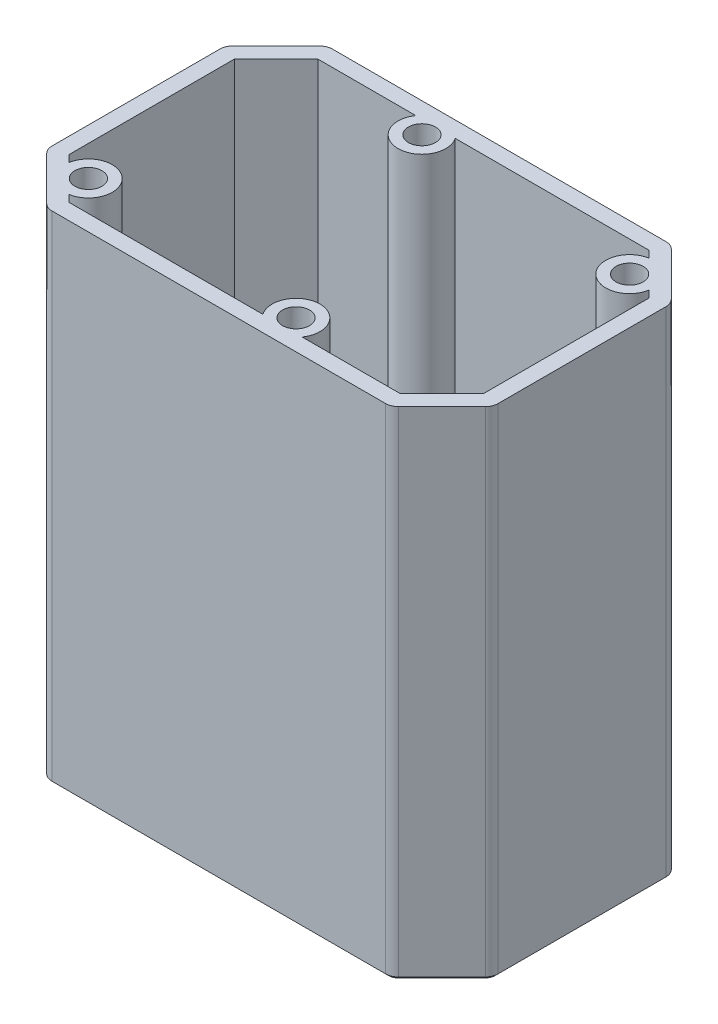
SolidWorks part; units mm, degrees
ref_plane "Front Plane" through (0, 0, 0) normal (0, 0, 1) x (1, 0, 0)
ref_plane "Top Plane" through (0, 0, 0) normal (0, 1, 0) x (1, 0, 0)
ref_plane "Right Plane" through (0, 0, 0) normal (1, 0, 0) x (0, 0, -1)
sketch "Sketch1" plane through (0, 0, 0) normal (0, 1, 0) x (1, 0, 0)
  line L0 (26.1716, 22) -> (-26.1716, 22)
  line L1 (-27.5858, 21.4142) -> (-34.4142, 14.5858)
  line L2 (-35, 13.1716) -> (-35, -13.1716)
  line L3 (-34.4142, -14.5858) -> (-27.5858, -21.4142)
  line L4 (-26.1716, -22) -> (26.1716, -22)
  line L5 (27.5858, -21.4142) -> (34.4142, -14.5858)
  line L6 (35, -13.1716) -> (35, 13.1716)
  line L7 (34.4142, 14.5858) -> (27.5858, 21.4142)
  line L8 (0, 22) -> (0, -22) construction
  line L9 (-32.5, 12.9645) -> (-32.5, -12.9645)
  line L10 (35, 0) -> (-35, 0) construction
  line L11 (-32.5, -12.9645) -> (-25.9645, -19.5)
  line L12 (-25.9645, -19.5) -> (25.9645, -19.5)
  line L13 (25.9645, -19.5) -> (32.5, -12.9645)
  line L14 (32.5, -12.9645) -> (32.5, 12.9645)
  line L15 (32.5, 12.9645) -> (25.9645, 19.5)
  line L16 (25.9645, 19.5) -> (-25.9645, 19.5)
  line L17 (-25.9645, 19.5) -> (-32.5, 12.9645)
  line L18 (-31, -18) -> (-29.2322, -16.2322) construction
  line L19 (31, 18) -> (29.2322, 16.2322) construction
  circle A3 centre (7.5, -17.375) radius 2.125
  circle A4 centre (27.7296, 14.7296) radius 2.125
  circle A5 centre (-7.5, 17.375) radius 2.125
  circle A6 centre (-27.7296, -14.7296) radius 2.125
  arc A9 (-26.1716, 22) -> (-27.5858, 21.4142) centre (-26.1716, 20) ccw
  arc A10 (-34.4142, 14.5858) -> (-35, 13.1716) centre (-33, 13.1716) ccw
  arc A11 (-35, -13.1716) -> (-34.4142, -14.5858) centre (-33, -13.1716) ccw
  arc A12 (-27.5858, -21.4142) -> (-26.1716, -22) centre (-26.1716, -20) ccw
  arc A13 (26.1716, -22) -> (27.5858, -21.4142) centre (26.1716, -20) ccw
  arc A14 (34.4142, -14.5858) -> (35, -13.1716) centre (33, -13.1716) ccw
  arc A15 (35, 13.1716) -> (34.4142, 14.5858) centre (33, 13.1716) ccw
  arc A16 (27.5858, 21.4142) -> (26.1716, 22) centre (26.1716, 20) ccw
  arc A21 (-32.5, -12.9645) -> (-32.5, -12.9645) centre (-32.5, -12.9645) ccw
  arc A22 (-25.9645, -19.5) -> (-25.9645, -19.5) centre (-25.9645, -19.5) ccw
  arc A23 (25.9645, -19.5) -> (25.9645, -19.5) centre (25.9645, -19.5) ccw
  arc A24 (32.5, -12.9645) -> (32.5, -12.9645) centre (32.5, -12.9645) ccw
  arc A25 (32.5, 12.9645) -> (32.5, 12.9645) centre (32.5, 12.9645) ccw
  arc A26 (25.9645, 19.5) -> (25.9645, 19.5) centre (25.9645, 19.5) ccw
  arc A27 (-25.9645, 19.5) -> (-25.9645, 19.5) centre (-25.9645, 19.5) ccw
  arc A28 (-32.5, 12.9645) -> (-32.5, 12.9645) centre (-32.5, 12.9645) ccw
  circle A29 centre (-7.5, 17.375) radius 3.75
  circle A30 centre (7.5, -17.375) radius 3.75
  circle A31 centre (27.7296, 14.7296) radius 3.75
  circle A32 centre (-27.7296, -14.7296) radius 3.75
  dimension "D2" = 7.5
  dimension "D4" = 4.25
  dimension "D1" = 44
  dimension "D5" = 70
  dimension "D6" = 27.5
  dimension "D7" = 27.5
  dimension "D3" = 2.5
extrude "Boss-Extrude1" add sketch "Sketch1" along normal blind 3 contours L4 A13 L5 A14 L6 A15 L7 A16 L0 A9 L1 A10 L2 A11 L3 A12
extrude "Boss-Extrude2" add sketch "Sketch1<4>" along normal blind 78 contours L7 A16 L0 A9 L1 A10 L2 A11 L3 A12 L4 A13 L5 A14 L6 A15 A32 L11 L9 L17 L16 A29 L15 A31 L14 L13 L12 A30 | L11 A32 A6 | L11 A32 | L12 A30 A3 | L12 A30 | L16 A29 | L16 A29 A5 | L15 A31 A4 | L15 A31 region at (26.6205, 0, -21.0839) region at (-27.3967, 0, 11.1) region at (-29.7016, 0, 16.7016) region at (-7.5, 0, -20.1638) region at (-9.0449, 0, -19.4047) region at (6.4157, 0, 13.8848) region at (7.5, 0, 20.1638) region at (29.7016, 0, -16.7016) region at (28.0654, 0, -17.2503)
sketch "Sketch1<4>" plane through (0, 0, 0) normal (0, 1, 0) x (1, 0, 0) same geometry as "Sketch1"
chamfer "Chamfer1" distance 0.5 angle 45 16 edges at (0, 0, 22) (26.9369, 0, 21.8478) (31, 0, 18) (34.8478, 0, 13.9369) (35, 0, 0) (34.8478, 0, -13.9369) (31, 0, -18) (26.9369, 0, -21.8478) (0, 0, -22) (-26.9369, 0, -21.8478) (-31, 0, -18) (-34.8478, 0, -13.9369) (-35, 0, 0) (-34.8478, 0, 13.9369) (-31, 0, 18) (-26.9369, 0, 21.8478)
